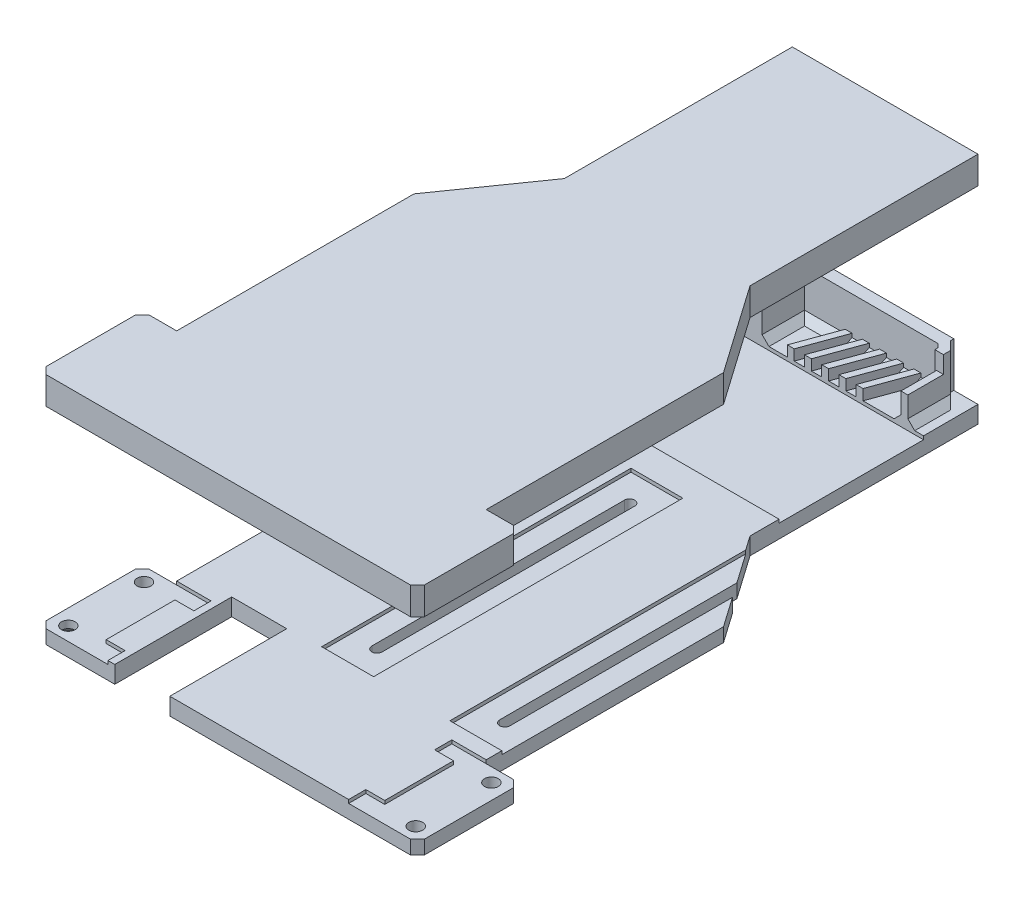
SolidWorks part; units mm, degrees
ref_plane "Front Plane" through (0, 0, 0) normal (0, 0, 1) x (1, 0, 0)
ref_plane "Top Plane" through (0, 0, 0) normal (0, 1, 0) x (1, 0, 0)
ref_plane "Right Plane" through (0, 0, 0) normal (1, 0, 0) x (0, 0, -1)
sketch "Sketch1" plane through (0, 0, 0) normal (0, 1, 0) x (1, 0, 0)
  line L1 (-45, 95) -> (45, 95)
  line L2 (-45, 95) -> (-45, -95)
  line L3 (-45, -95) -> (45, -95)
  line L4 (45, 95) -> (45, -95)
  line L5 (-45, 95) -> (45, -95) construction
  line L6 (-45, -95) -> (45, 95) construction
  point P0 (0, 0)
  dimension "D1" = 190
  dimension "D2" = 90
extrude "Boss-Extrude1" add sketch "Sketch1" along normal blind 5 contours L2 L1 L4 L3
sketch "Sketch2" plane through (0, 0, 0) normal (0, 1, 0) x (1, 0, 0)
  line L0 (-45, 95) -> (-45, -95) construction
  line L1 (-45, -65) -> (-55, -65)
  line L2 (-45, -65) -> (-45, -95)
  line L3 (-45, -95) -> (-55, -95)
  line L4 (-55, -65) -> (-55, -95)
  line L5 (45, 95) -> (45, -95) construction
  line L6 (45, -65) -> (55, -65)
  line L7 (45, -65) -> (45, -95)
  line L8 (45, -95) -> (55, -95)
  line L9 (55, -65) -> (55, -95)
  line L10 (-45, -95) -> (45, -95) construction
  dimension "D1" = 30
  dimension "D2" = 10
extrude "Boss-Extrude2" add sketch "Sketch2" along normal blind 5
chamfer "Chamfer1" distance 2 angle 45 4 edges at (55, 2.5, 95) (55, 2.5, 65) (-55, 2.5, 95) (-55, 2.5, 65)
sketch "Sketch3" plane through (0, 5, 0) normal (0, 1, 0) x (1, 0, 0)
  line L0 (-53, -95) -> (53, -95) construction
  line L1 (-33, -95) -> (-17, -95)
  line L2 (-33, -95) -> (-33, -61)
  line L3 (-33, -61) -> (-17, -61)
  line L4 (-17, -95) -> (-17, -61)
  line L5 (-55, -67) -> (-55, -93) construction
  dimension "D1" = 22
  dimension "D2" = 16
  dimension "D3" = 34
extrude "Cut-Extrude1" cut sketch "Sketch3" against normal blind 50 contours L2 L1 L4 L3
sketch "Sketch4" plane through (0, 5, 0) normal (0, 1, 0) x (1, 0, 0)
  line L0 (-45, 80.1598) -> (-45, 38.1598)
  line L1 (-45, 95) -> (-45, -65) construction
  line L2 (-48, 80.1598) -> (48, 80.1598) construction
  line L4 (-45, 38.1598) -> (45, 38.1598)
  line L5 (45, 95) -> (45, -65) construction
  line L6 (45, 38.1598) -> (45, 80.1598)
  line L7 (45, 80.1598) -> (-45, 80.1598)
  dimension "D1" = 42
extrude "Cut-Extrude2" cut sketch "Sketch4" against normal blind 1
sketch "Sketch7" plane through (0, 5, 0) normal (0, 1, 0) x (1, 0, 0)
  line L0 (-7.3823, 29.4629) -> (-7.3823, -60.4534)
  line L1 (-7.3823, -60.4534) -> (7.7177, -60.4534)
  line L2 (7.7177, -60.4534) -> (7.7177, 29.4629)
  line L3 (7.7177, 29.4629) -> (-7.3823, 29.4629)
  line L4 (29.9, 29.4629) -> (29.9, -60.4534)
  line L5 (29.9, -60.4534) -> (45, -60.4534)
  line L6 (45, 38.1598) -> (45, -65) construction
  line L7 (45, -60.4534) -> (45, 29.4629)
  line L8 (45, 29.4629) -> (29.9, 29.4629)
  line M17 (45, -65) -> (45, 38.1598)
  dimension "D1" = 15.1
  dimension "D2" = 15.1
extrude "Cut-Extrude7" cut sketch "Sketch7" against normal blind 1 contours L8 L4 L5 M17 | L3 L0 L1 L2
sketch "Sketch17" plane through (0, 0, 0) normal (0, 1, 0) x (1, 0, 0)
  line L0 (-19.94, 80.1598) -> (-19.94, 92.4998)
  line L1 (45, 80.1598) -> (-45, 80.1598) construction
  line L2 (-19.94, 69.0848) -> (-19.94, 88.4854) construction
  line L4 (-19.94, 92.4998) -> (18.94, 92.4998)
  line L5 (18.94, 92.4998) -> (19.94, 91.4998)
  line L6 (19.94, 90.5) -> (22.44, 90.5)
  line L7 (19.94, 91.4998) -> (18.94, 92.4998) construction
  line L9 (-45, 95) -> (45, 95) construction
  line L10 (19.94, 91.4998) -> (19.94, 90.5)
  line L12 (-22.44, 80.1598) -> (-22.44, 94.9998)
  line L14 (-22.44, 94.9998) -> (19.9756, 94.9998)
  line L15 (19.9756, 94.9998) -> (22.44, 92.5354)
  line L16 (22.44, 92.5354) -> (22.44, 90.5)
  line L17 (-22.44, 80.1598) -> (-19.94, 80.1598)
  line L21 (-22.44, 80.1598) -> (-22.44, 92.5354) construction
  line L22 (-19.94, 80.1598) -> (-19.94, 91.4998) construction
  line L23 (-19.94, 91.4998) -> (-18.94, 92.4998) construction
  line L24 (-18.94, 92.4998) -> (18.94, 92.4998) construction
  line L25 (-19.9756, 94.9998) -> (19.9756, 94.9998) construction
  line L26 (-22.44, 92.5354) -> (-19.9756, 94.9998) construction
  line L28 (19.94, 91.4998) -> (19.94, 80.1598) construction
  line L30 (22.44, 92.5354) -> (22.44, 80.1598) construction
  dimension "D2" = 4.5
  dimension "D3" = 2.0354
  dimension "D1" = 2.5
extrude "Boss-Extrude4" add sketch "Sketch17" along normal blind 13 from surface at 5 starting at face at (0, 5, -87.5799)
sketch "Sketch18" plane through (0, 5, 0) normal (0, 1, 0) x (1, 0, 0)
  line L6 (-12.5996, 80.1598) -> (-10.5996, 80.1598)
  line L7 (45, 80.1598) -> (-19.94, 80.1598) construction
  line L8 (-10.5996, 80.1598) -> (-6.1082, 92.4998)
  line L9 (-19.94, 92.4998) -> (18.94, 92.4998) construction
  line L10 (-6.1082, 92.4998) -> (-8.1082, 92.4998)
  line L11 (-8.1082, 92.4998) -> (-12.5996, 80.1598)
  line L12 (-3.1082, 92.4998) -> (-7.5996, 80.1598)
  line L13 (-7.5996, 80.1598) -> (-5.5996, 80.1598)
  line L14 (-5.5996, 80.1598) -> (-1.1082, 92.4998)
  line L15 (-1.1082, 92.4998) -> (-3.1082, 92.4998)
  line L16 (1.8918, 92.4998) -> (-2.5996, 80.1598)
  line L17 (-2.5996, 80.1598) -> (-0.5996, 80.1598)
  line L18 (-0.5996, 80.1598) -> (3.8918, 92.4998)
  line L19 (3.8918, 92.4998) -> (1.8918, 92.4998)
  line L20 (6.8918, 92.4998) -> (2.4004, 80.1598)
  line L21 (2.4004, 80.1598) -> (4.4004, 80.1598)
  line L22 (4.4004, 80.1598) -> (8.8918, 92.4998)
  line L23 (8.8918, 92.4998) -> (6.8918, 92.4998)
  line L24 (11.8918, 92.4998) -> (7.4004, 80.1598)
  line L25 (7.4004, 80.1598) -> (9.4004, 80.1598)
  line L26 (9.4004, 80.1598) -> (13.8918, 92.4998)
  line L27 (13.8918, 92.4998) -> (11.8918, 92.4998)
  dimension "D1" = 2
  dimension "D2" = 70
  dimension "D3" = 5
extrude "Boss-Extrude5" add sketch "Sketch18" along normal blind 3.1
sketch "Sketch19" plane through (0, 0, 0) normal (0, 1, 0) x (1, 0, 0)
  line L0 (-35, -65) -> (-35, -70)
  line L1 (-35, -70) -> (-40.5, -70)
  line L2 (-40.5, -70) -> (-40.5, -90)
  line L3 (-40.5, -90) -> (-35, -90)
  line L4 (-35, -90) -> (-35, -95)
  line L5 (-53, -95) -> (-33, -95) construction
  line L6 (-35, -95) -> (-53, -95)
  line L7 (-53, -95) -> (-55, -93)
  line L8 (-55, -93) -> (-55, -67)
  line L9 (-55, -67) -> (-53, -65)
  line L10 (-53, -65) -> (-35, -65)
extrude "Cut-Extrude11" cut sketch "Sketch19" against normal blind 1 from surface at 5 starting at face at (-6.8539, 5, -86.3298)
mirror "Mirror1" about plane through (0, 0, 0) normal (1, 0, 0) of "Cut-Extrude11"
sketch "Sketch20" plane through (0, 0, 0) normal (0, 1, 0) x (1, 0, 0)
  line L0 (-27, 29.7067) -> (-45, 4)
  line L1 (-45, 95) -> (-27, 95)
  line L4 (-27, 95) -> (-27, 29.7067)
  line L5 (-45, 38.1598) -> (-45, -65) construction
  line L8 (-45, 95) -> (-45, 4)
  line L9 (0, 0) -> (0, -50000) construction
  line L10 (27, 95) -> (27, 29.7067)
  line L11 (45, 95) -> (27, 95)
  line L12 (45, 95) -> (45, 4)
  line L13 (27, 29.7067) -> (45, 4)
  dimension "D1" = 18
  dimension "D2" = 35
  dimension "D3" = 4
extrude "Cut-Extrude12" cut sketch "Sketch20" against normal through all both and the other way through all
sketch "Sketch22" plane through (0, 0, -94.9998) normal (0, 0, -1) x (-1, 0, 0)
  line L0 (-19.9756, 5) -> (-27, 5)
  line L4 (-19.9756, 5) -> (22.44, 5)
  line L5 (22.44, 5) -> (22.44, 18)
  line L6 (22.44, 18) -> (-19.9756, 18)
  line L7 (-19.9756, 18) -> (-19.9756, 5)
  line L9 (22.44, 5) -> (22.44, 18)
  line L10 (22.44, 18) -> (-19.9756, 18)
  line L11 (-19.9756, 18) -> (-19.9756, 5)
  line L12 (27, 0) -> (27, 5)
  line L13 (27, 5) -> (-27, 5)
  line L14 (-27, 5) -> (-27, 0)
  line L15 (-27, 0) -> (27, 0)
  line L16 (27, 0) -> (27, 5)
  line L17 (27, 5) -> (22.44, 5)
  line L18 (-27, 5) -> (-27, 0)
  line L19 (-27, 0) -> (27, 0)
  dimension "D1" = 0
  dimension "D2" = 0
extrude "Boss-Extrude6" add sketch "Sketch22" along normal blind 1 contours L9 L10 L11 L0 L18 L19 L16 L17
chamfer "Chamfer4" distance 2 3 edges at (-14.0241, 5, -92.4998) (-4.6082, 5, -92.4998) (-19.94, 5, -86.3298)
sketch "Sketch23" plane through (0, 0, 0) normal (0, -1, 0) x (1, 0, 0)
  line L0 (-55, 67) -> (-55, 93) construction
  line L1 (-53, 95) -> (-33, 95) construction
  line L2 (-45, 65) -> (-53, 65) construction
  line L3 (0, 0) -> (0, 50000) construction
  circle A0 centre (-50.5, 91) radius 2
  circle A1 centre (-50.5, 69) radius 2
  circle A2 centre (50.5, 69) radius 2
  circle A3 centre (50.5, 91) radius 2
  dimension "D1" = 4
  dimension "D2" = 4.5
  dimension "D3" = 4
  dimension "D4" = 4
extrude "Cut-Extrude13" cut sketch "Sketch23" against normal up to next
sketch "Sketch25" plane through (0, 0, 0) normal (0, -1, 0) x (1, 0, 0)
  line L0 (0.2177, 51.9887) -> (0.2177, -21.4629) construction
  line L1 (1.7177, 51.9887) -> (1.7177, -21.4629)
  line L2 (-1.2823, 51.9887) -> (-1.2823, -21.4629)
  line L3 (37.4, 51.9887) -> (37.4, -21.4629) construction
  line L4 (38.9, 51.9887) -> (38.9, -21.4629)
  line L5 (35.9, 51.9887) -> (35.9, -21.4629)
  line L6 (7.7177, -29.4629) -> (-7.3823, -29.4629) construction
  circle A0 centre (37.4, 51.9887) radius 1.4 construction
  circle A1 centre (37.4, -2.9886) radius 1.4 construction
  circle A2 centre (0.2177, -2.9886) radius 1.4 construction
  circle A3 centre (0.2177, 51.9887) radius 1.4 construction
  circle A4 centre (37.4, 51.9887) radius 1.4 construction
  circle A5 centre (37.4, -2.9886) radius 1.4 construction
  circle A6 centre (0.2177, -2.9886) radius 1.4 construction
  circle A7 centre (0.2177, 51.9887) radius 1.4 construction
  arc A8 (1.7177, 51.9887) -> (-1.2823, 51.9887) centre (0.2177, 51.9887) ccw
  arc A9 (-1.2823, -21.4629) -> (1.7177, -21.4629) centre (0.2177, -21.4629) ccw
  arc A10 (38.9, 51.9887) -> (35.9, 51.9887) centre (37.4, 51.9887) ccw
  arc A11 (35.9, -21.4629) -> (38.9, -21.4629) centre (37.4, -21.4629) ccw
  point P14 (0.2177, 15.2629)
  point P21 (37.4, 15.2629)
  point P26 (0, 0)
  point P27 (0, 0)
  point P28 (0.2177, 51.9887)
  point P29 (0, 0)
  dimension "D2" = 1.5
  dimension "D1" = 8
extrude "Cut-Extrude14" cut sketch "Sketch25" against normal through all both and the other way through all
sketch "Sketch26" plane through (0, 0, 0) normal (0, -1, 0) x (1, 0, 0)
  circle A1 centre (-50.5, 91) radius 3.8
  circle A2 centre (-50.5, 91) radius 2 construction
  dimension "D1" = 7.6
extrude "Cut-Extrude15" cut sketch "Sketch26" against normal blind 2.5 draft 44 and the other way through all
sketch "Sketch27" plane through (0, 5, 0) normal (0, 1, 0) x (1, 0, 0)
  line L0 (20.4373, 80.1598) -> (20.4373, 90.5)
  line L1 (27, 80.1598) -> (-27, 80.1598) construction
  line L2 (19.94, 90.5) -> (22.44, 90.5) construction
  line L3 (20.4373, 90.5) -> (22.44, 90.5)
  line L4 (22.44, 90.5) -> (22.44, 80.1598)
  line L5 (22.44, 80.1598) -> (20.4373, 80.1598)
  line L6 (19.94, 91.4998) -> (19.94, 90.5) construction
  dimension "D1" = 0.4973
extrude "Boss-Extrude7" add sketch "Sketch27" along normal blind 8
chamfer "Chamfer5" distance 2 1 edges at (22.44, 5, -86.3476)
chamfer "Chamfer6" distance 4.6 angle 73 1 edges at (-22.44, 5, -88.0798)
chamfer "Chamfer7" distance 2 5 edges at (20.1887, 5, -90.5) (19.44, 5, -91.9998) (19.94, 5, -90.9999) (16.4159, 5, -92.4998) (20.4373, 5, -85.3299)
sketch "Sketch28" plane through (0, 0, 0) normal (0, 1, 0) x (1, 0, 0)
  line L0 (-53, -95) -> (-35, -95) construction
  line L1 (-53, -95) -> (-55, -93)
  line L2 (-55, -67) -> (-55, -93) construction
  line L3 (-55, -93) -> (-53, -95) construction
  line L4 (-55, -93) -> (-55, -67)
  line L5 (-53, -65) -> (-55, -67) construction
  line L6 (-55, -67) -> (-53, -65)
  line L7 (-53, -65) -> (-45, -65)
  line L8 (-35, -65) -> (-45, -65) construction
  line L9 (-45, 4) -> (-45, -65) construction
  line L10 (-45, -65) -> (-45, 4)
  line L11 (-27, 29.7067) -> (-45, 4) construction
  line L12 (-45, 4) -> (-27, 29.7067)
  line L13 (-27, 29.7067) -> (-27, 95.9998)
  line L14 (-27, 80.1598) -> (-27, 95.9998) construction
  line L15 (-27, 95.9998) -> (27, 95.9998)
  line L16 (27, 80.1598) -> (27, 95.9998) construction
  line L17 (27, 95.9998) -> (27, 29.7067)
  line L18 (29.9, 25.565) -> (27, 29.7067) construction
  line L19 (27, 29.7067) -> (45, 4)
  line L20 (45, 4) -> (45, -65)
  line L21 (45, -60.4534) -> (45, -65) construction
  line L22 (45, -65) -> (53, -65) construction
  line L23 (45, -65) -> (53, -65)
  line L24 (53, -65) -> (55, -67)
  line L25 (53, -65) -> (55, -67) construction
  line L26 (55, -67) -> (55, -93) construction
  line L27 (55, -67) -> (55, -93)
  line L28 (55, -93) -> (53, -95)
  line L29 (55, -93) -> (53, -95) construction
  line L30 (53, -95) -> (-53, -95)
  line L31 (45, -60.4534) -> (45, 4) construction
  point P24 (45, 4)
  point P47 (45, -7.6994)
extrude "Boss-Extrude8" add sketch "Sketch28" along normal blind 8 from offset 60 separate body
